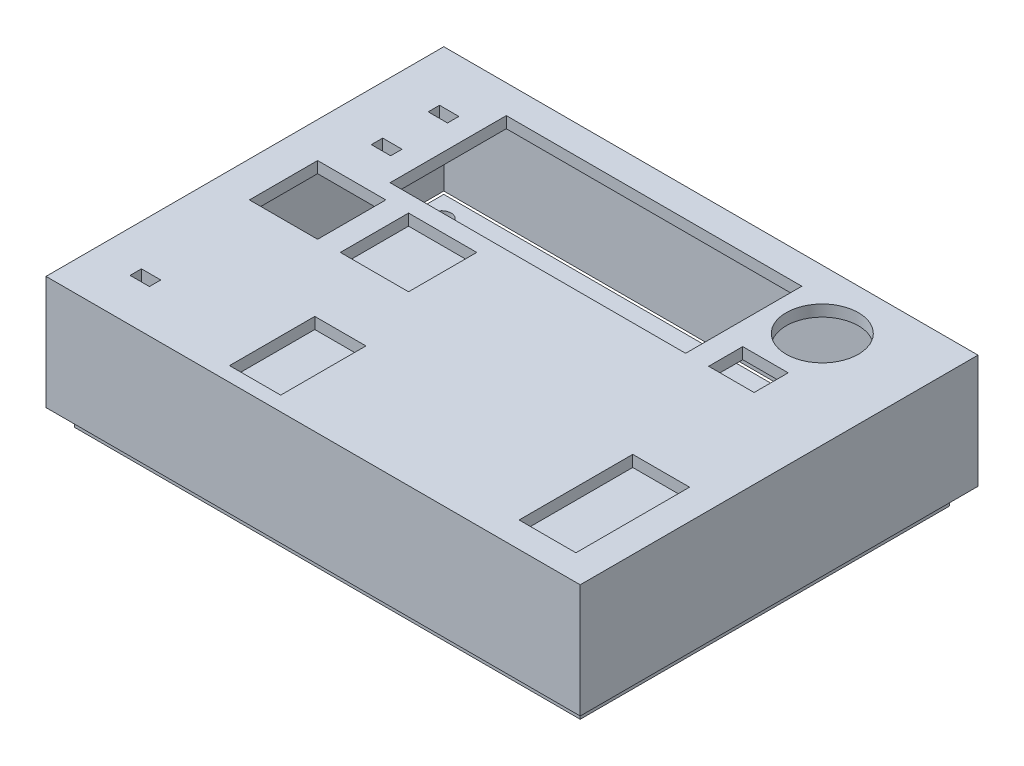
SolidWorks part; units mm, degrees
ref_plane "Front Plane" through (0, 0, 0) normal (0, 0, 1) x (1, 0, 0)
ref_plane "Top Plane" through (0, 0, 0) normal (0, 1, 0) x (1, 0, 0)
ref_plane "Right Plane" through (0, 0, 0) normal (1, 0, 0) x (0, 0, -1)
sketch "Sketch1" plane through (0, 0, 0) normal (0, 1, 0) x (1, 0, 0)
  line L0 (26.25, 25.8869) -> (18.25, 25.8869)
  line L7 (-53.75, -24.7156) -> (40.25, -24.7156)
  line L8 (-53.75, -24.7156) -> (-53.75, 45.2844)
  line L9 (-53.75, 45.2844) -> (40.25, 45.2844)
  line L10 (40.25, -24.7156) -> (40.25, 45.2844)
  line L11 (-41.8, 23.9844) -> (-45.2, 23.9844)
  line L15 (-37.75, 40.2844) -> (14.25, 40.2844)
  line L16 (-37.75, 40.2844) -> (-37.75, 19.8328)
  line L17 (-37.75, 19.8328) -> (14.25, 19.8328)
  line L18 (14.25, 40.2844) -> (14.25, 19.8328)
  line L21 (18.25, 19.8869) -> (26.25, 19.8869)
  line L22 (26.25, 25.8869) -> (26.25, 19.8869)
  line L27 (18.25, 25.8869) -> (18.25, 19.8869)
  line L28 (-47.5027, 16.8328) -> (-35.5027, 16.8328)
  line L29 (-47.5027, 16.8328) -> (-47.5027, 4.8328)
  line L30 (-47.5027, 4.8328) -> (-35.5027, 4.8328)
  line L31 (-35.5027, 16.8328) -> (-35.5027, 4.8328)
  line L33 (-31.5027, 16.8328) -> (-31.5027, 4.8328)
  line L34 (-19.5027, 4.8328) -> (-31.5027, 4.8328)
  line L35 (-19.5027, 16.8328) -> (-19.5027, 4.8328)
  line L36 (-19.5027, 16.8328) -> (-31.5027, 16.8328)
  line L41 (-41.8, 33.9844) -> (-45.2, 33.9844)
  line L42 (-41.8, 33.9844) -> (-41.8, 35.9844)
  line L43 (-41.8, 35.9844) -> (-45.2, 35.9844)
  line L44 (-45.2, 33.9844) -> (-45.2, 35.9844)
  line L45 (-41.8, 23.9844) -> (-41.8, 25.9844)
  line L46 (-41.8, 25.9844) -> (-45.2, 25.9844)
  line L47 (-45.2, 23.9844) -> (-45.2, 25.9844)
  line L48 (-15.0027, -22.1672) -> (-24.0027, -22.1672)
  line L49 (-15.0027, -22.1672) -> (-15.0027, -7.1672)
  line L50 (-15.0027, -7.1672) -> (-24.0027, -7.1672)
  line L51 (-24.0027, -22.1672) -> (-24.0027, -7.1672)
  line L52 (34.9973, -20.2156) -> (24.9973, -20.2156)
  line L53 (34.9973, -20.2156) -> (34.9973, -0.2156)
  line L54 (34.9973, -0.2156) -> (24.9973, -0.2156)
  line L55 (24.9973, -20.2156) -> (24.9973, -0.2156)
  line L56 (-43.1027, -17.1672) -> (-46.5027, -17.1672)
  line L61 (-43.1027, -17.1672) -> (-43.1027, -15.1672)
  line L62 (-43.1027, -15.1672) -> (-46.5027, -15.1672)
  line L63 (-46.5027, -17.1672) -> (-46.5027, -15.1672)
  circle A0 centre (23.25, 34.8869) radius 6.35
  point P0 (0, 0)
  point P6 (-6.75, 10.2844)
  dimension "D7" = 4
  dimension "D2" = 94
  dimension "D9" = 9
  dimension "D3" = 47
  dimension "D4" = 52
  dimension "D5" = 16
  dimension "D6" = 5
  dimension "D8" = 26
  dimension "D10" = 9
  dimension "D11" = 3
  dimension "D12" = 4
  dimension "D13" = 4.3
  dimension "D14" = 15
  dimension "D15" = 4.05
  dimension "D16" = 2
  dimension "D17" = 3.4
  dimension "D18" = 4.05
  dimension "D19" = 3.4
  dimension "D20" = 12
  dimension "D21" = 2
  dimension "D22" = 9
  dimension "D23" = 40
  dimension "D24" = 20
  dimension "D25" = 4.5
  dimension "D26" = 12
  dimension "D27" = 4
  dimension "D28" = 12
  dimension "D29" = 3
  dimension "D30" = 33.7527
  dimension "D31" = 10
  dimension "D32" = 4.5
  dimension "D33" = 3.4
  dimension "D34" = 2
  dimension "D35" = 20
  dimension "D36" = 1
extrude "Boss-Extrude1" add sketch "Sketch1" along normal blind 2
sketch "Sketch2" plane through (0, 0, 0) normal (0, 1, 0) x (1, 0, 0)
  line L0 (-51.75, -22.7156) -> (38.25, -22.7156)
  line L1 (-53.75, 45.2844) -> (40.25, 45.2844)
  line L2 (-53.75, 45.2844) -> (-53.75, -24.7156)
  line L3 (-53.75, -24.7156) -> (40.25, -24.7156)
  line L4 (40.25, 45.2844) -> (40.25, -24.7156)
  line L9 (38.25, 43.2844) -> (38.25, -22.7156)
  line L13 (-51.75, -22.7156) -> (-51.75, 43.2844)
  line L14 (38.25, 43.2844) -> (-51.75, 43.2844)
  line L15 (31.6771, 43.2268) -> (-51.75, -22.7156) construction
  point P6 (-10, 10.2844)
  dimension "D1" = 66
  dimension "D2" = 2
  dimension "D3" = 2
  dimension "D4" = 2
extrude "Boss-Extrude2" add sketch "Sketch2" along normal blind 1 and the other way blind 18
sketch "Sketch3" plane through (40.25, 0, 0) normal (1, 0, 0) x (0, 0, -1)
  line L0 (-7.0156, -6.7933) -> (-14.0156, -6.7933)
  line L1 (-7.0156, -6.7933) -> (-7.0156, -1)
  line L2 (-7.0156, -1) -> (-14.0156, -1)
  line L3 (-14.0156, -6.7933) -> (-14.0156, -1)
extrude "Cut-Extrude1" cut sketch "Sketch3" against normal blind 10 and the other way blind 10 from surface starting at face at (-53.75, -8, -10.2844)
sketch "Sketch4" plane through (0, -18, 0) normal (0, -1, 0) x (1, 0, 0)
  line L0 (37.75, -42.7844) -> (37.75, 22.2156)
  line L5 (37.75, 22.2156) -> (-51.25, 22.2156)
  line L6 (-51.25, 22.2156) -> (-51.25, -42.7844)
  line L7 (-51.25, -42.7844) -> (37.75, -42.7844)
extrude "Boss-Extrude3" add sketch "Sketch4" along normal blind 3 separate body
sketch "Sketch5" plane through (0, -21, 0) normal (0, -1, 0) x (-1, 0, 0)
  line L0 (51.25, 42.7844) -> (-37.75, 42.7844) construction
  line L1 (-37.75, 42.7844) -> (-37.75, -22.2156) construction
  line L2 (51.25, -22.2156) -> (51.25, 42.7844) construction
  line L3 (-37.75, -22.2156) -> (51.25, -22.2156) construction
  circle A3 centre (-34.75, 39.7844) radius 1.7
  circle A4 centre (35.25, -15.1156) radius 1.7
  circle A5 centre (47.75, 38.8844) radius 1.7
  dimension "D1" = 3
  dimension "D3" = 3.9
  dimension "D5" = 16
  dimension "D2" = 3
  dimension "D4" = 3.5
  dimension "D6" = 7.1
extrude "Cut-Extrude5" cut sketch "Sketch5" against normal blind 3
